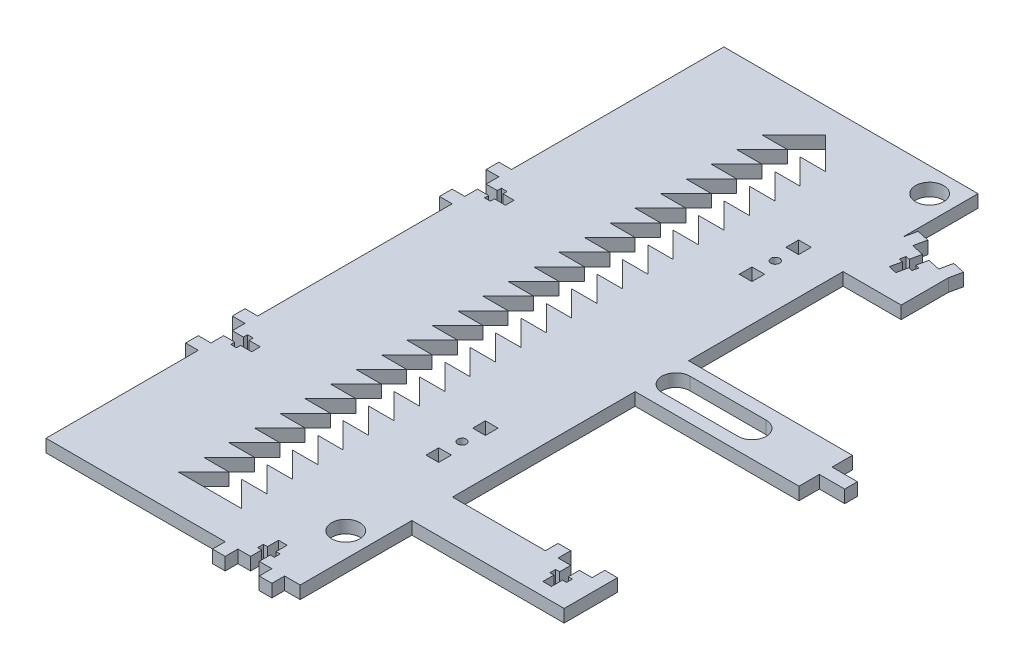
SolidWorks part; units mm, degrees
ref_plane "Front Plane" through (0, 0, 0) normal (0, 0, 1) x (1, 0, 0)
ref_plane "Top Plane" through (0, 0, 0) normal (0, 1, 0) x (1, 0, 0)
ref_plane "Right Plane" through (0, 0, 0) normal (1, 0, 0) x (0, 0, -1)
sketch "Axle Support Plate" plane through (0, 0, 0) normal (0, 1, 0) x (1, 0, 0)
  line L0 (51.4759, 157.4574) -> (51.4759, -134.6426) construction
  line L1 (38.7759, 169.5676) -> (38.7759, -103.4054) construction
  line L2 (0, 156.8676) -> (-15.875, 140.9926)
  line L3 (-15.875, 140.9926) -> (-3.175, 140.9926)
  line L4 (63.5861, -169.5676) -> (63.5861, -113.6876)
  line L5 (-63.5861, 169.5676) -> (63.5861, -169.5676) construction
  line L6 (-63.5861, -169.5676) -> (63.5861, 169.5676) construction
  line L7 (-63.5861, -63.6496) -> (-63.5861, 33.6324)
  line L8 (-63.5861, 169.5676) -> (63.5861, 169.5676)
  line L9 (0, 169.5676) -> (0, -169.5676) construction
  line L10 (15.875, 140.9926) -> (0, 156.8676)
  line L11 (-3.175, 140.9926) -> (-15.875, 128.2926)
  line L12 (-15.875, 128.2926) -> (-3.175, 128.2926)
  line L13 (15.875, 128.2926) -> (3.175, 140.9926)
  line L14 (-3.175, 128.2926) -> (-15.875, 115.5926)
  line L15 (-15.875, 115.5926) -> (-3.175, 115.5926)
  line L16 (15.875, 115.5926) -> (3.175, 128.2926)
  line L17 (63.5861, 11.4074) -> (4.2777, 11.4074) construction
  line L18 (-3.175, 115.5926) -> (-15.875, 102.8926)
  line L19 (-15.875, 102.8926) -> (-3.175, 102.8926)
  line L20 (15.875, 102.8926) -> (3.175, 115.5926)
  line L21 (-3.175, 102.8926) -> (-15.875, 90.1926)
  line L22 (-15.875, 90.1926) -> (-3.175, 90.1926)
  line L23 (55.7939, -169.5676) -> (63.5861, -169.5676)
  line L24 (15.875, 90.1926) -> (3.175, 102.8926)
  line L25 (-3.175, 90.1926) -> (-15.875, 77.4926)
  line L26 (-15.875, 77.4926) -> (-3.175, 77.4926)
  line L27 (15.875, 77.4926) -> (3.175, 90.1926)
  line L28 (-3.175, 77.4926) -> (-15.875, 64.7926)
  line L29 (-15.875, 64.7926) -> (-3.175, 64.7926)
  line L30 (15.875, 64.7926) -> (3.175, 77.4926)
  line L31 (-3.175, 64.7926) -> (-15.875, 52.0926)
  line L32 (-15.875, 52.0926) -> (-3.175, 52.0926)
  line L33 (15.875, 52.0926) -> (3.175, 64.7926)
  line L34 (-3.175, 52.0926) -> (-15.875, 39.3926)
  line L35 (-15.875, 39.3926) -> (-3.175, 39.3926)
  line L36 (15.875, 39.3926) -> (3.175, 52.0926)
  line L37 (63.5861, 24.7876) -> (145.5462, 24.7876)
  line L38 (145.5462, 24.7876) -> (145.5462, 14.5824)
  line L39 (145.5462, -1.9727) -> (63.5861, -1.9727)
  line L40 (70.6162, 11.4074) -> (108.7162, 11.4074) construction
  line L41 (70.6162, 18.4376) -> (108.7162, 18.4376)
  line L42 (70.6162, 4.3773) -> (108.7162, 4.3773)
  line L43 (145.5462, 8.2324) -> (158.2462, 8.2324)
  line L44 (158.2462, 8.2324) -> (158.2462, 14.5824)
  line L45 (158.2462, 14.5824) -> (145.5462, 14.5824)
  line L46 (63.5861, 24.7876) -> (63.5861, 169.5676)
  line L47 (63.5861, 24.7876) -> (63.5861, -1.9727) construction
  line L48 (63.5861, 11.4074) -> (158.2462, 11.4074) construction
  line L49 (-3.175, 39.3926) -> (-15.875, 26.6926)
  line L50 (-15.875, 26.6926) -> (-3.175, 26.6926)
  line L51 (145.5462, 8.2324) -> (145.5462, -1.9727)
  line L52 (15.875, 26.6926) -> (3.175, 39.3926)
  line L53 (-3.175, 26.6926) -> (-15.875, 13.9926)
  line L54 (-15.875, 13.9926) -> (-3.175, 13.9926)
  line L55 (15.875, 13.9926) -> (3.175, 26.6926)
  line L56 (-3.175, 13.9926) -> (-15.875, 1.2926)
  line L57 (-15.875, 1.2926) -> (-3.175, 1.2926)
  line L58 (15.875, 1.2926) -> (3.175, 13.9926)
  line L59 (3.175, -11.4074) -> (15.875, -11.4074)
  line L60 (-15.875, -11.4074) -> (-3.175, -11.4074)
  line L61 (15.875, -11.4074) -> (3.175, 1.2926)
  line L62 (-3.175, -11.4074) -> (-15.875, -24.1074)
  line L63 (-15.875, -24.1074) -> (-3.175, -24.1074)
  line L64 (15.875, -24.1074) -> (3.175, -11.4074)
  line L65 (-3.175, -24.1074) -> (-15.875, -36.8074)
  line L66 (-15.875, -36.8074) -> (-3.175, -36.8074)
  line L67 (15.875, -36.8074) -> (3.175, -24.1074)
  line L68 (-3.175, -36.8074) -> (-15.875, -49.5074)
  line L69 (-15.875, -49.5074) -> (-3.175, -49.5074)
  line L70 (15.875, -49.5074) -> (3.175, -36.8074)
  line L71 (-3.175, -49.5074) -> (-15.875, -62.2074)
  line L72 (-15.875, -62.2074) -> (-3.175, -62.2074)
  line L73 (15.875, -62.2074) -> (3.175, -49.5074)
  line L74 (-3.175, -62.2074) -> (-15.875, -74.9074)
  line L75 (-15.875, -74.9074) -> (-3.175, -74.9074)
  line L76 (15.875, -74.9074) -> (3.175, -62.2074)
  line L77 (-3.175, -74.9074) -> (-15.875, -87.6074)
  line L78 (-15.875, -87.6074) -> (-3.175, -87.6074)
  line L79 (15.875, -87.6074) -> (3.175, -74.9074)
  line L80 (-3.175, -87.6074) -> (-15.875, -100.3074)
  line L81 (-63.5861, 63.3504) -> (-63.5861, 169.5676)
  line L82 (-15.875, -100.3074) -> (-3.175, -100.3074)
  line L83 (15.875, -100.3074) -> (3.175, -87.6074)
  line L84 (-3.175, -100.3074) -> (-15.875, -113.0074)
  line L85 (-15.875, -113.0074) -> (-3.175, -113.0074)
  line L86 (15.875, -113.0074) -> (3.175, -100.3074)
  line L87 (-3.175, -113.0074) -> (-15.875, -125.7074)
  line L88 (-15.875, -125.7074) -> (-3.175, -125.7074)
  line L89 (15.875, -125.7074) -> (3.175, -113.0074)
  line L90 (26.0759, -169.5676) -> (-63.5861, -169.5676)
  line L91 (-3.175, -125.7074) -> (-15.875, -138.4074)
  line L92 (-15.875, -138.4074) -> (-3.175, -138.4074)
  line L93 (15.875, -138.4074) -> (3.175, -125.7074)
  line L94 (-63.5861, -169.5676) -> (-63.5861, -93.3676)
  line L95 (-3.175, -138.4074) -> (-15.875, -151.1074)
  line L96 (-15.875, -151.1074) -> (15.875, -151.1074)
  line L97 (15.875, -151.1074) -> (3.175, -138.4074)
  line L98 (3.175, 140.9926) -> (15.875, 140.9926)
  line L99 (3.175, 115.5926) -> (15.875, 115.5926)
  line L100 (3.175, 128.2926) -> (15.875, 128.2926)
  line L101 (3.175, 102.8926) -> (15.875, 102.8926)
  line L102 (3.175, 77.4926) -> (15.875, 77.4926)
  line L103 (3.175, 90.1926) -> (15.875, 90.1926)
  line L104 (3.175, 64.7926) -> (15.875, 64.7926)
  line L105 (3.175, 52.0926) -> (15.875, 52.0926)
  line L106 (3.175, 39.3926) -> (15.875, 39.3926)
  line L107 (3.175, 26.6926) -> (15.875, 26.6926)
  line L108 (3.175, 13.9926) -> (15.875, 13.9926)
  line L109 (3.175, 1.2926) -> (15.875, 1.2926)
  line L110 (-3.175, 1.2926) -> (-15.875, -11.4074)
  line L111 (0, 4.4676) -> (-1.2184, 3.2492) [skipped]
  line L112 (3.175, -24.1074) -> (15.875, -24.1074)
  line L113 (3.175, -36.8074) -> (15.875, -36.8074)
  line L114 (3.175, -49.5074) -> (15.875, -49.5074)
  line L115 (3.175, -62.2074) -> (15.875, -62.2074)
  line L116 (3.175, -74.9074) -> (15.875, -74.9074)
  line L117 (3.175, -87.6074) -> (15.875, -87.6074)
  line L118 (3.175, -100.3074) -> (15.875, -100.3074)
  line L119 (3.175, -113.0074) -> (15.875, -113.0074)
  line L120 (3.175, -125.7074) -> (15.875, -125.7074)
  line L121 (3.175, -138.4074) -> (15.875, -138.4074)
  line L122 (139.7861, -93.3676) -> (139.7861, -113.6876)
  line L123 (139.7861, -113.6876) -> (63.5861, -113.6876)
  line L124 (110.0681, -93.3676) -> (63.5861, -93.3676)
  line L125 (63.5861, -93.3676) -> (63.5861, -1.9727)
  circle A0 centre (51.4759, 157.4574) radius 7.0301
  circle A1 centre (51.4759, -134.6426) radius 7.0301
  arc A4 (70.6162, 18.4376) -> (70.6162, 4.3773) centre (70.6162, 11.4074) ccw
  arc A5 (108.7162, 4.3773) -> (108.7162, 18.4376) centre (108.7162, 11.4074) ccw
  point P8 (0, 0)
  point P15 (51.4759, 11.4074)
  point P57 (89.6662, 11.4074)
  line B0 (-63.5861, -69.9996) -> (-69.9361, -69.9996)
  line B1 (-69.9361, -69.9996) -> (-69.9361, -63.6496)
  line B2 (-69.9361, -63.6496) -> (-63.5861, -63.6496)
  line B3 (-63.5861, -76.3496) -> (-58.0511, -76.3496)
  line B4 (-58.0511, -76.3496) -> (-58.0511, -74.3086)
  line B5 (-58.0511, -74.3086) -> (-55.1511, -74.3086)
  line B6 (-55.1511, -74.3086) -> (-55.1511, -76.3496)
  line B7 (-55.1511, -76.3496) -> (-49.6161, -76.3496)
  line B8 (-49.6161, -76.3496) -> (-49.6161, -80.6676)
  line B9 (-49.6161, -80.6676) -> (-55.1511, -80.6676)
  line B10 (-55.1511, -80.6676) -> (-55.1511, -82.7086)
  line B11 (-55.1511, -82.7086) -> (-58.0511, -82.7086)
  line B12 (-58.0511, -82.7086) -> (-58.0511, -80.6676)
  line B13 (-58.0511, -80.6676) -> (-63.5861, -80.6676)
  line B14 (-49.6161, -78.5086) -> (-63.5861, -78.5086) construction
  line B15 (-63.5861, -87.0176) -> (-63.5861, -80.6676)
  line B16 (-69.9361, -93.3676) -> (-63.5861, -93.3676)
  line B17 (-63.5861, -69.9996) -> (-63.5861, -76.3496)
  line B18 (-69.9361, -87.0176) -> (-69.9361, -93.3676)
  line B19 (-63.5861, -87.0176) -> (-69.9361, -87.0176)
  line B20 (-63.5861, 57.0004) -> (-69.9361, 57.0004)
  line B21 (-69.9361, 57.0004) -> (-69.9361, 63.3504)
  line B22 (-69.9361, 63.3504) -> (-63.5861, 63.3504)
  line B23 (-63.5861, 50.6504) -> (-58.0511, 50.6504)
  line B24 (-58.0511, 50.6504) -> (-58.0511, 52.6914)
  line B25 (-58.0511, 52.6914) -> (-55.1511, 52.6914)
  line B26 (-55.1511, 52.6914) -> (-55.1511, 50.6504)
  line B27 (-55.1511, 50.6504) -> (-49.6161, 50.6504)
  line B28 (-49.6161, 50.6504) -> (-49.6161, 46.3324)
  line B29 (-49.6161, 46.3324) -> (-55.1511, 46.3324)
  line B30 (-55.1511, 46.3324) -> (-55.1511, 44.2914)
  line B31 (-55.1511, 44.2914) -> (-58.0511, 44.2914)
  line B32 (-58.0511, 44.2914) -> (-58.0511, 46.3324)
  line B33 (-58.0511, 46.3324) -> (-63.5861, 46.3324)
  line B34 (-49.6161, 48.4914) -> (-63.5861, 48.4914) construction
  line B35 (-63.5861, 39.9824) -> (-63.5861, 46.3324)
  line B36 (-69.9361, 33.6324) -> (-63.5861, 33.6324)
  line B37 (-63.5861, 57.0004) -> (-63.5861, 50.6504)
  line B38 (-69.9361, 39.9824) -> (-69.9361, 33.6324)
  line B39 (-63.5861, 39.9824) -> (-69.9361, 39.9824)
  line B40 (32.4259, -169.5676) -> (32.4259, -175.9176)
  line B41 (32.4259, -175.9176) -> (26.0759, -175.9176)
  line B42 (26.0759, -175.9176) -> (26.0759, -169.5676)
  line B43 (38.7759, -169.5676) -> (38.7759, -164.0326)
  line B44 (38.7759, -164.0326) -> (36.7349, -164.0326)
  line B45 (36.7349, -164.0326) -> (36.7349, -161.1326)
  line B46 (36.7349, -161.1326) -> (38.7759, -161.1326)
  line B47 (38.7759, -161.1326) -> (38.7759, -155.5976)
  line B48 (38.7759, -155.5976) -> (43.0939, -155.5976)
  line B49 (43.0939, -155.5976) -> (43.0939, -161.1326)
  line B50 (43.0939, -161.1326) -> (45.1349, -161.1326)
  line B51 (45.1349, -161.1326) -> (45.1349, -164.0326)
  line B52 (45.1349, -164.0326) -> (43.0939, -164.0326)
  line B53 (43.0939, -164.0326) -> (43.0939, -169.5676)
  line B54 (40.9349, -155.5976) -> (40.9349, -169.5676) construction
  line B55 (49.4439, -169.5676) -> (43.0939, -169.5676)
  line B56 (55.7939, -175.9176) -> (55.7939, -169.5676)
  line B57 (32.4259, -169.5676) -> (38.7759, -169.5676)
  line B58 (49.4439, -175.9176) -> (55.7939, -175.9176)
  line B59 (49.4439, -169.5676) -> (49.4439, -175.9176)
  line B60 (41.9509, 74.9074) -> (41.9509, 104.6254) construction
  line B61 (39.7919, 89.7664) -> (44.1099, 89.7664) construction
  line B62 (38.7759, 98.2754) -> (45.1259, 98.2754)
  line B63 (38.7759, 98.2754) -> (38.7759, 104.6254)
  line B64 (38.7759, 104.6254) -> (45.1259, 104.6254)
  line B65 (45.1259, 98.2754) -> (45.1259, 104.6254)
  line B66 (38.7759, 98.2754) -> (45.1259, 104.6254) construction
  line B67 (38.7759, 104.6254) -> (45.1259, 98.2754) construction
  line B68 (38.7759, 74.9074) -> (45.1259, 81.2574) construction
  line B69 (38.7759, 81.2574) -> (45.1259, 74.9074) construction
  line B70 (45.1259, 81.2574) -> (45.1259, 74.9074)
  line B71 (38.7759, 74.9074) -> (45.1259, 74.9074)
  line B72 (38.7759, 81.2574) -> (38.7759, 74.9074)
  line B73 (38.7759, 81.2574) -> (45.1259, 81.2574)
  circle B74 centre (41.9509, 89.7664) radius 2.159
  line B75 (41.9509, -52.0926) -> (41.9509, -81.8106) construction
  line B76 (39.7919, -66.9516) -> (44.1099, -66.9516) construction
  line B77 (38.7759, -75.4606) -> (45.1259, -75.4606)
  line B78 (38.7759, -75.4606) -> (38.7759, -81.8106)
  line B79 (38.7759, -81.8106) -> (45.1259, -81.8106)
  line B80 (45.1259, -75.4606) -> (45.1259, -81.8106)
  line B81 (38.7759, -75.4606) -> (45.1259, -81.8106) construction
  line B82 (38.7759, -81.8106) -> (45.1259, -75.4606) construction
  line B83 (38.7759, -52.0926) -> (45.1259, -58.4426) construction
  line B84 (38.7759, -58.4426) -> (45.1259, -52.0926) construction
  line B85 (45.1259, -58.4426) -> (45.1259, -52.0926)
  line B86 (38.7759, -52.0926) -> (45.1259, -52.0926)
  line B87 (38.7759, -58.4426) -> (38.7759, -52.0926)
  line B88 (38.7759, -58.4426) -> (45.1259, -58.4426)
  circle B89 centre (41.9509, -66.9516) radius 2.159
  line B90 (133.4361, -93.3676) -> (133.4361, -87.0176)
  line B91 (133.4361, -87.0176) -> (139.7861, -87.0176)
  line B92 (139.7861, -87.0176) -> (139.7861, -93.3676)
  line B93 (127.0861, -93.3676) -> (127.0861, -98.9026)
  line B94 (127.0861, -98.9026) -> (129.1271, -98.9026)
  line B95 (129.1271, -98.9026) -> (129.1271, -101.8026)
  line B96 (129.1271, -101.8026) -> (127.0861, -101.8026)
  line B97 (127.0861, -101.8026) -> (127.0861, -107.3376)
  line B98 (127.0861, -107.3376) -> (122.7681, -107.3376)
  line B99 (122.7681, -107.3376) -> (122.7681, -101.8026)
  line B100 (122.7681, -101.8026) -> (120.7271, -101.8026)
  line B101 (120.7271, -101.8026) -> (120.7271, -98.9026)
  line B102 (120.7271, -98.9026) -> (122.7681, -98.9026)
  line B103 (122.7681, -98.9026) -> (122.7681, -93.3676)
  line B104 (124.9271, -107.3376) -> (124.9271, -93.3676) construction
  line B105 (116.4181, -93.3676) -> (122.7681, -93.3676)
  line B106 (110.0681, -87.0176) -> (110.0681, -93.3676)
  line B107 (133.4361, -93.3676) -> (127.0861, -93.3676)
  line B108 (116.4181, -87.0176) -> (110.0681, -87.0176)
  line B109 (116.4181, -93.3676) -> (116.4181, -87.0176)
  dimension "D1" = 5.08
  dimension "D4" = 14.0603
  dimension "D5" = 5.08
  dimension "D8" = 31.75
  dimension "D14" = 14.0603
  dimension "D15" = 76.2
  dimension "D16" = 6.35
  dimension "D22" = 7.0301
  dimension "D25" = 36.83
  dimension "D2" = 292.1
  dimension "D6" = 12.7
  dimension "D7" = 63.5
  dimension "D9" = 89.662
  dimension "D10" = 12.7
  dimension "D11" = 24
  dimension "D12" = 10.541
  dimension "D13" = 34.925
  dimension "D17" = 76.2
  dimension "D23" = 6.35
  dimension "D24" = 38.1
  dimension "D26" = 12.7
  dimension "D27" = 6.35
  dimension "D29" = 76.2
  dimension "D30" = 203.2
sketch_block_instance "Male T-slot assembly-1"
sketch_block "Male T-slot assembly" parameters "D1"=6.35, "D2"=6.35, "D3"=4.318, "D4"=2.9, "D5"=8.4, "D6"=13.97, "D7"=6.35
sketch_block_instance "Male T-slot assembly-2"
sketch_block_instance "Male T-slot assembly-4"
sketch_block_instance "Female T-Slot Assembly-1"
sketch_block "Female T-Slot Assembly" parameters "D4"=4.318, "D1"=6.35, "D2"=6.35, "D3"=6.35
sketch_block_instance "Female T-Slot Assembly-3"
sketch_block_instance "Male T-slot assembly-6"
extrude "Boss-Extrude1" add sketch "Axle Support Plate" along normal blind 6.35 contours L23 L4 L39 L51 L43 L44 L45 L38 L37 L46 L8 region at (59.69, 0, 165.4272)
sketch "Sketch1" plane through (0, 6.35, 0) normal (0, 1, 0) x (1, 0, 0)
  line L0 (63.5861, 24.7876) -> (63.5861, 169.5676) construction
  line L1 (92.6228, 125.7308) -> (92.6228, 102.0848)
  line L2 (92.6228, 102.0848) -> (63.5861, 102.0848)
  line L3 (44.4458, 157.4574) -> (58.5061, 157.4574) construction
  line L4 (51.4759, 164.4876) -> (51.4759, 150.4273) construction
  line L5 (63.5861, 102.0848) -> (63.5861, 132.0574)
  circle A0 centre (51.4759, 157.4574) radius 7.0301 construction
  point P12 (51.4759, 157.4574)
  line B0 (86.4184, 127.0827) -> (87.7702, 133.2871)
  line B1 (87.7702, 133.2871) -> (93.9747, 131.9353)
  line B2 (93.9747, 131.9353) -> (92.6228, 125.7308)
  line B3 (80.214, 128.4345) -> (79.0356, 123.0264)
  line B4 (79.0356, 123.0264) -> (81.0298, 122.5919)
  line B5 (81.0298, 122.5919) -> (80.4125, 119.7584)
  line B6 (80.4125, 119.7584) -> (78.4182, 120.1929)
  line B7 (78.4182, 120.1929) -> (77.2399, 114.7848)
  line B8 (77.2399, 114.7848) -> (73.0209, 115.704)
  line B9 (73.0209, 115.704) -> (74.1992, 121.1121)
  line B10 (74.1992, 121.1121) -> (72.205, 121.5466)
  line B11 (72.205, 121.5466) -> (72.8224, 124.3801)
  line B12 (72.8224, 124.3801) -> (74.8166, 123.9456)
  line B13 (74.8166, 123.9456) -> (75.9949, 129.3538)
  line B14 (75.1304, 115.2444) -> (78.1044, 128.8941) construction
  line B15 (69.7905, 130.7056) -> (75.9949, 129.3538)
  line B16 (64.9379, 138.2619) -> (63.5861, 132.0574)
  line B17 (86.4184, 127.0827) -> (80.214, 128.4345)
  line B18 (71.1423, 136.91) -> (64.9379, 138.2619)
  line B19 (69.7905, 130.7056) -> (71.1423, 136.91)
  dimension "D1" = 12.292
  dimension "D2" = 12.7
  dimension "D3" = 25.4
sketch_block_instance "Male T-slot assembly-9"
extrude "Boss-Extrude2" add sketch "Sketch1" against normal blind 6.35 contours B15 B19 B18 B16 L5 L2 L1 B2 B1 B0 B17 B3 B4 B5 B6 B7 B8 B9 B10 B11 B12 B13 region at (77.7452, 6.35, -116.6392)
equation "\"Ball Diameter\"= 1.75in"
equation "\"Sheet Thickness\"= 0.25in"
equation "\"Screw Diameter\"= .17in"
equation "\"Robot Diameter\"= 14in"
equation "\"Castor Screw Diameter\"= 0.22in"
equation "\"Wheel Diameter\" = 4in"
equation "\"Nut Diameter\" = 8.4mm"
equation "\"Nut Height\" = 2.9mm"
equation "\"Screw Height\" = 0.55in"
equation "\"Pulley Diameter\" = 1in"
equation "\"Reactor Height\" = 14in"
equation "\"Elevator Height\" = 11.5in"
equation "\"Elevator Width\" = \"Ball Diameter\" + 0.25in"
equation "\"D1@Boss-Extrude1\"=\"Sheet Thickness\""
equation "\"Elevator Bearing Diameter\" = sqr(2*(\"Sheet Thickness\"^2)) + 0.2in"
equation "\"Elevator Axle Length\" = \"Elevator Width\" + 8*\"Sheet Thickness\""
equation "\"D4@Axle Support Plate\"=\"Elevator Bearing Diameter\""
equation "\"D6@Axle Support Plate\"=(\"Pulley Diameter\")/2"
equation "\"D13@Axle Support Plate\"=2.5in - \"Sheet Thickness\" - (\"Ball Diameter\")/2"
equation "\"D9@Axle Support Plate\"=\"Elevator Clearance from Axis\" + \"Sheet Thickness\""
equation "\"D14@Axle Support Plate\" = \"Elevator Bearing Diameter\""
equation "\"D22@Axle Support Plate\"=\"Elevator Bearing Diameter\"/2"
equation "\"D23@Axle Support Plate\" = \"Sheet Thickness\""
equation "\"Elevator Axle Endcap Diameter\" = \"Pulley Diameter\" + 0.25in"
equation "\"D25@Axle Support Plate\"=\"Elevator Axle Endcap Diameter\"+0.2in"
equation "\"D27@Axle Support Plate\"=\"Sheet Thickness\""
equation "\"Elevator Clearance from Axis\" = 3.28in"
